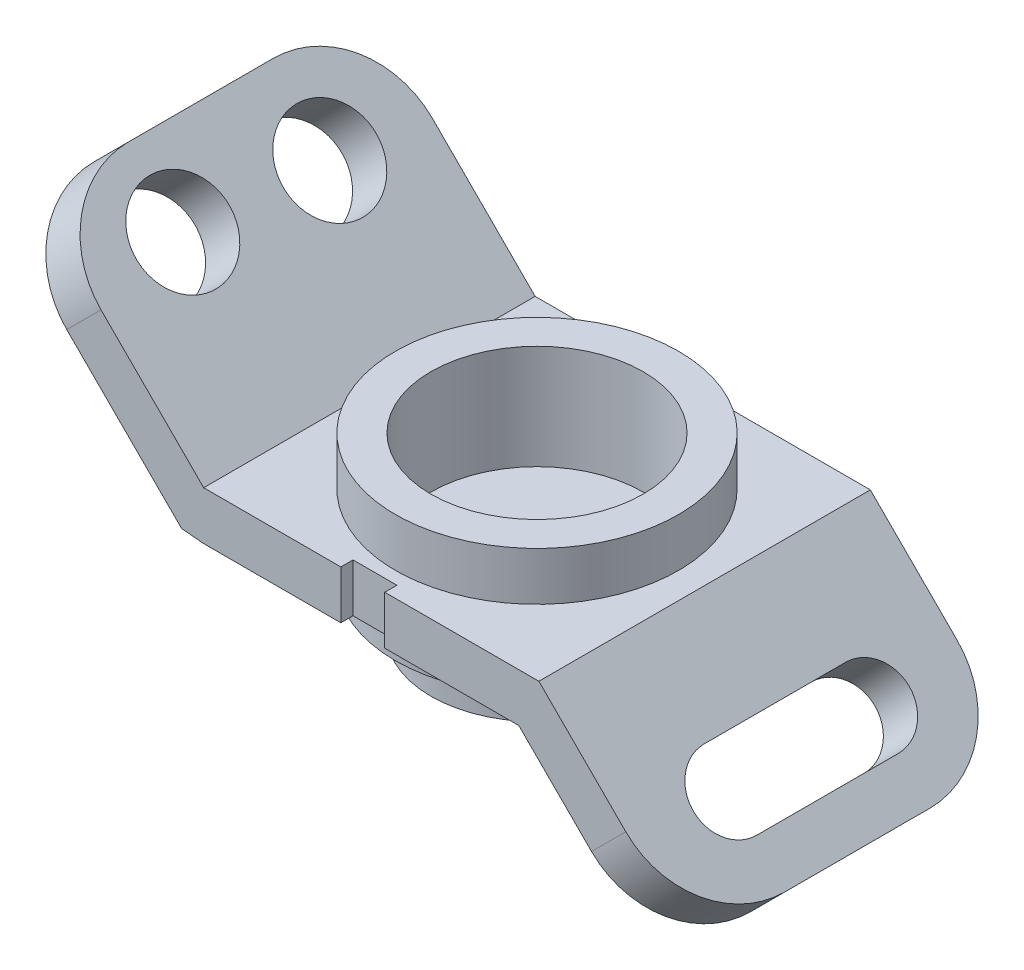
SolidWorks part; units mm, degrees
ref_plane "정면" through (0, 0, 0) normal (0, 0, 1) x (1, 0, 0)
ref_plane "윗면" through (0, 0, 0) normal (0, 1, 0) x (1, 0, 0)
ref_plane "우측면" through (0, 0, 0) normal (1, 0, 0) x (0, 0, -1)
sketch "스케치2" plane through (0, 0, 0) normal (0, 1, 0) x (1, 0, 0)
  line L1 (-45, -44.5) -> (45, -44.5)
  line L2 (-45, -44.5) -> (-45, 44.5)
  line L3 (-45, 44.5) -> (45, 44.5)
  line L4 (45, -44.5) -> (45, 44.5)
  line L5 (-45, -44.5) -> (45, 44.5) construction
  line L6 (-45, 44.5) -> (45, -44.5) construction
  point P0 (0, 0)
  dimension "D1" = 90
  dimension "D2" = 89
extrude "보스-돌출1" add sketch "스케치2" along normal blind 13 contours L3 L4 L1 L2
ref_plane "평면1" through (29, 29, 0) normal (-0.7071, -0.7071, 0) x (0, 0, -1)
sketch "스케치3" plane through (29, 29, 0) normal (-0.7071, -0.7071, 0) x (0, 0, -1)
  line L0 (-44.5, 22.6274) -> (-44.5, 80.6274)
  line L1 (-44.5, 80.6274) -> (44.5, 80.6274)
  line L2 (44.5, 80.6274) -> (44.5, 22.6274)
  line L3 (44.5, 22.6274) -> (-44.5, 22.6274)
extrude "보스-돌출2" add sketch "스케치3" along normal blind 13 contours L0 L1 L2 L3
fillet "필렛1" radius 25 2 edges at (81.416, -32.6084, -44.5) (81.416, -32.6084, 44.5)
ref_plane "평면2" through (-16, -16, 0) normal (-0.7071, -0.7071, 0) x (0, 0, -1)
sketch "스케치4" plane through (-16, -16, 0) normal (-0.7071, -0.7071, 0) x (0, 0, -1)
  line L0 (44.5, -41.0122) -> (44.5, -105.0122)
  line L2 (-44.5, -41.0122) -> (-44.5, -105.0122)
  line L3 (-44.5, -105.0122) -> (44.5, -105.0122)
  line L4 (44.5, -41.0122) -> (44.5, -31.8198)
  line L6 (-44.5, -31.8198) -> (-44.5, -41.0122)
  line L7 (44.5, -36.416) -> (-44.5, -36.416)
extrude "보스-돌출4" add sketch "스케치4" along normal blind 13 contours L4 L7 L6 L2 L3 L0 region at (-66.0024, 34.0024, 0)
sketch "스케치5" plane through (-16, -16, 0) normal (0.7071, 0.7071, 0) x (0, 0, -1)
  line L0 (-44.5, 105.0122) -> (44.5, 105.0122) construction
  circle A0 centre (-19, 85.0122) radius 12.5
  circle A1 centre (18.9383, 82.8479) radius 12.5
  dimension "D1" = 25
  dimension "D2" = 25
  dimension "D3" = 38
  dimension "D4" = 20
  dimension "D5" = 19
extrude "컷-돌출1" cut sketch "스케치5" against normal through all contours A0 | A1 region at (-76.1127, 44.1127, 19) region at (-74.5823, 42.5823, -18.9383)
fillet "필렛2" radius 25 2 edges at (-94.851, 53.6586, -44.5) (-94.851, 53.6586, 44.5)
sketch "스케치6" plane through (29, 29, 0) normal (0.7071, 0.7071, 0) x (0, 0, -1)
  line L0 (-18.5065, -58.6274) -> (19.4935, -58.6274) construction
  line L1 (-18.5065, -48.6274) -> (19.4935, -48.6274)
  line L2 (-18.5065, -68.6274) -> (19.4935, -68.6274)
  line L3 (-19.5, -80.6274) -> (19.5, -80.6274) construction
  arc A0 (-18.5065, -48.6274) -> (-18.5065, -68.6274) centre (-18.5065, -58.6274) ccw
  arc A1 (19.4935, -68.6274) -> (19.4935, -48.6274) centre (19.4935, -58.6274) ccw
  point P2 (0.4935, -58.6274)
  dimension "D2" = 10
  dimension "D1" = 38
  dimension "D3" = 22
extrude "컷-돌출2" cut sketch "스케치6" against normal through all contours L1 A1 L2 A0
sketch "스케치7" plane through (0, 13, 0) normal (0, 1, 0) x (1, 0, 0)
  circle A0 centre (0, 0) radius 38
  circle A1 centre (0, 0) radius 28.5
  circle A2 centre (0, 0) radius 12.5
extrude "보스-돌출5" add sketch "스케치7" along normal blind 13 contours A0
extrude "컷-돌출3" cut sketch "스케치7<3>" along normal blind 13 and the other way blind 19 contours A1
sketch "스케치7<3>" plane through (0, 13, 0) normal (0, 1, 0) x (1, 0, 0) same geometry as "스케치7"
extrude "보스-돌출6" add sketch "스케치7<4>" against normal blind 21 from offset 13 separate body contours A1 offset against normal yes
sketch "스케치7<4>" plane through (0, 13, 0) normal (0, 1, 0) x (1, 0, 0) same geometry as "스케치7"
extrude "컷-돌출4" cut sketch "스케치7<5>" against normal through all contours A2
sketch "스케치7<5>" plane through (0, 13, 0) normal (0, 1, 0) x (1, 0, 0) same geometry as "스케치7"
sketch "스케치8" plane through (0, 13, 0) normal (0, 1, 0) x (1, 0, 0)
  line L0 (-8.1712, 44.5) -> (-8.1712, 41.2334)
  line L1 (-45, 44.5) -> (45, 44.5) construction
  line L2 (-8.1712, 41.2334) -> (3.6098, 41.2334)
  line L3 (3.6098, 41.2334) -> (3.6098, 44.5)
  line L4 (3.6098, 44.5) -> (-8.1712, 44.5)
  line L5 (0, 0) -> (26.3149, 0) construction
  line L6 (3.6098, -41.2334) -> (3.6098, -44.5)
  line L7 (-8.1712, -44.5) -> (-8.1712, -41.2334)
  line L8 (-8.1712, -41.2334) -> (3.6098, -41.2334)
  line L9 (3.6098, -44.5) -> (-8.1712, -44.5)
extrude "컷-돌출5" cut sketch "스케치8" against normal blind 21 contours L8 L6 L9 L7 | L2 L3 L4 L0
sketch "스케치9" plane through (0, 0, -44.5) normal (0, 0, -1) x (-1, 0, 0)
  line L0 (45, 6.5) -> (45, 0)
  line L1 (45, 0) -> (50.9424, 0.5576)
  line L2 (50.9424, 0.5576) -> (45, 6.5)
extrude "보스-돌출7" add sketch "스케치9" against normal blind 89
extrude "보스-돌출8" add sketch "스케치7<6>" against normal blind 21 contours A0
sketch "스케치7<6>" plane through (0, 13, 0) normal (0, 1, 0) x (1, 0, 0) same geometry as "스케치7"
extrude "컷-돌출6" cut sketch "스케치7<7>" against normal blind 15 contours A1
sketch "스케치7<7>" plane through (0, 13, 0) normal (0, 1, 0) x (1, 0, 0) same geometry as "스케치7"
